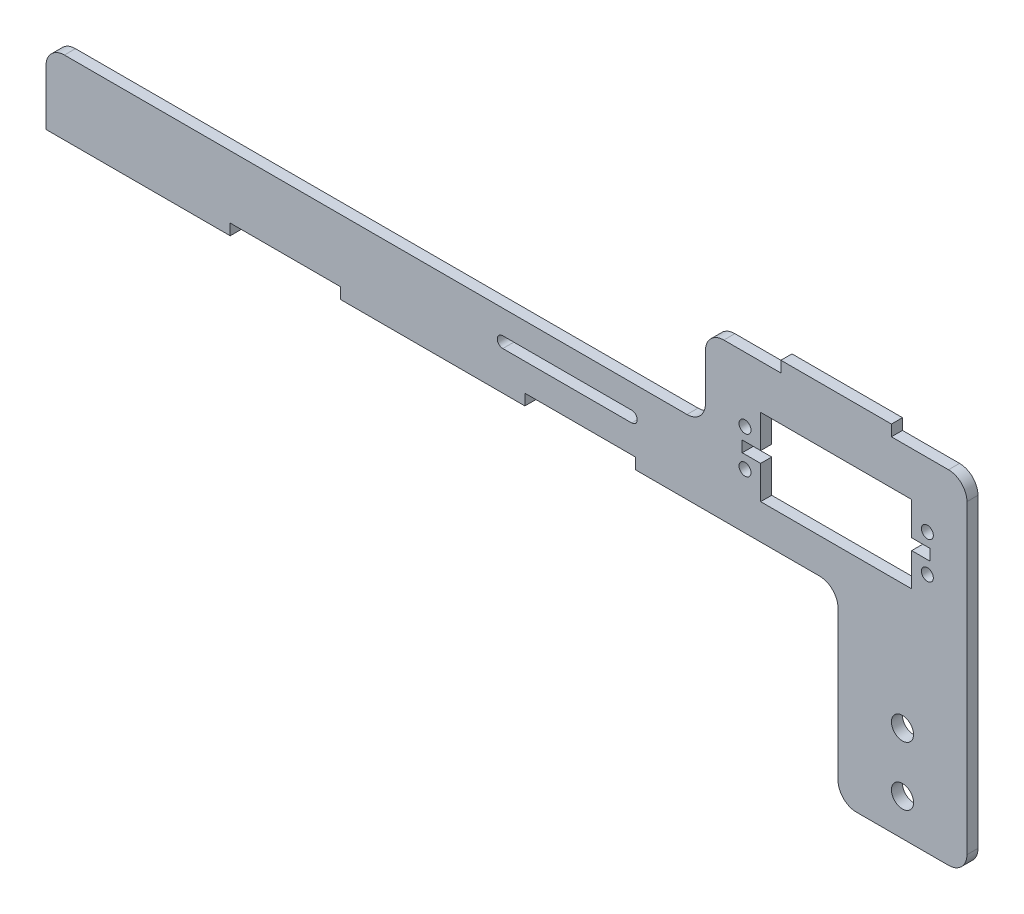
SolidWorks part; units mm, degrees
ref_plane "Plano frontal" through (0, 0, 0) normal (0, 0, 1) x (1, 0, 0)
ref_plane "Plano superior" through (0, 0, 0) normal (0, 1, 0) x (1, 0, 0)
ref_plane "Plano direito" through (0, 0, 0) normal (1, 0, 0) x (0, 0, -1)
sketch "Esboço1" plane through (0, 0, 0) normal (0, 0, 1) x (1, 0, 0)
  line L0 (194, 0) -> (235, 0) construction
  line L1 (215, -20) -> (160, -20)
  line L2 (250, -20) -> (250, 22.5)
  line L4 (0, -20) -> (0, 0)
  line L5 (194, 10.5) -> (235, 10.5)
  line L6 (194, 10.5) -> (194, -10.5)
  line L7 (194, -10.5) -> (235, -10.5)
  line L8 (235, 10.5) -> (235, -10.5)
  line L9 (214.5, 10.5) -> (214.5, -10.5) construction
  line L10 (0, 0) -> (179, 0)
  line L11 (179, 0) -> (179, 22.5)
  line L12 (250, 0) -> (184.4373, 0) construction
  line L13 (50, -20) -> (50, -17)
  line L14 (50, -17) -> (80, -17)
  line L15 (80, -17) -> (80, -20)
  line L16 (130, -20) -> (130, -17)
  line L17 (130, -17) -> (160, -17)
  line L18 (160, -17) -> (160, -20)
  line L19 (50, -20) -> (0, -20)
  line L20 (130, -20) -> (80, -20)
  line L21 (124, -8) -> (159, -8) construction
  line L22 (124, -6.5) -> (159, -6.5)
  line L23 (124, -9.5) -> (159, -9.5)
  line L26 (215, -20) -> (215, -70.5)
  line L27 (215, -70.5) -> (250, -70.5)
  line L28 (250, -20) -> (250, -70.5)
  line L29 (194, 1.5) -> (189, 1.5)
  line L30 (189, 1.5) -> (189, -1.5)
  line L31 (189, -1.5) -> (194, -1.5)
  line L32 (235, 1.5) -> (240, 1.5)
  line L33 (240, 1.5) -> (240, -1.5)
  line L34 (240, -1.5) -> (235, -1.5)
  line L36 (229.5, 25.5) -> (199.5, 25.5)
  line L37 (229.5, 25.5) -> (229.5, 22.5)
  line L38 (229.5, 22.5) -> (199.5, 22.5)
  line L39 (199.5, 25.5) -> (199.5, 22.5)
  line L40 (229.5, 25.5) -> (199.5, 22.5) construction
  line L41 (229.5, 22.5) -> (199.5, 25.5) construction
  line L42 (179, 22.5) -> (250, 22.5)
  circle A0 centre (189.75, 5) radius 1.625
  circle A1 centre (239.25, 5) radius 1.625
  circle A2 centre (239.25, -5) radius 1.625
  circle A3 centre (189.75, -5) radius 1.625
  arc A5 (124, -6.5) -> (124, -9.5) centre (124, -8) ccw
  arc A6 (159, -9.5) -> (159, -6.5) centre (159, -8) ccw
  circle A7 centre (232.5, -60.5) radius 3
  circle A8 centre (232.5, -44.5) radius 3
  point P36 (141.5, -8)
  point P51 (189, 0)
  point P52 (0, 0)
  point P57 (214.5, 24)
  point P62 (214.5, 20)
  dimension "D8" = 3.25
  dimension "D9" = 10
  dimension "D19" = 1.5
  dimension "D27" = 6
  dimension "D29" = 10
  dimension "D30" = 6
  dimension "D3" = 41
  dimension "D4" = 15
  dimension "D5" = 21
  dimension "D6" = 35
  dimension "D7" = 49.5
  dimension "D10" = 20
  dimension "D11" = 15
  dimension "D12" = 179
  dimension "D13" = 50
  dimension "D14" = 30
  dimension "D15" = 3
  dimension "D16" = 50
  dimension "D17" = 30
  dimension "D18" = 3
  dimension "D20" = 8
  dimension "D21" = 35
  dimension "D22" = 20
  dimension "D23" = 12
  dimension "D25" = 9.5
  dimension "D28" = 50.5
  dimension "D31" = 16
  dimension "D32" = 3
  dimension "D33" = 5
  dimension "D34" = 3
  dimension "D35" = 30
extrude "Ressalto-extrusão1" add sketch "Esboço1" along normal blind 3 contours L20 L16 L17 L18 L1 L2 L11 L10 L4 L19 L13 L14 L15 A1 A0 L5 L8 L7 L6 A2 A3 | L36 L39 L37 region at (159.6775, -14.7785, 0) region at (214.5, 24, 0)
fillet "Filete1" radius 5 7 edges at (215, -20, 1.5) (215, -70.5, 1.5) (250, -70.5, 1.5) (179, 0, 1.5) (0, 0, 1.5) (179, 22.5, 1.5) (250, 22.5, 1.5)
